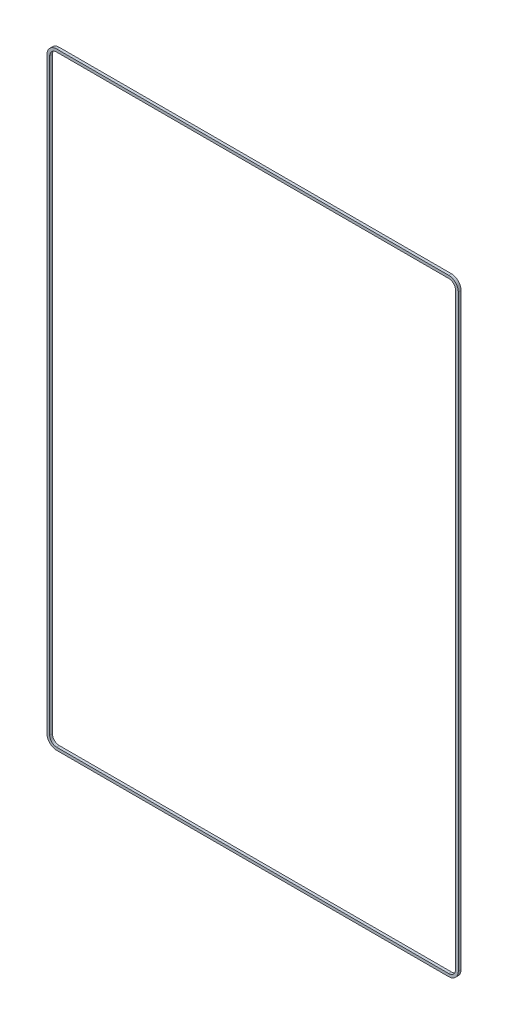
SolidWorks part; units mm, degrees
ref_plane "Front Plane" through (0, 0, 0) normal (0, 0, 1) x (1, 0, 0)
ref_plane "Top Plane" through (0, 0, 0) normal (0, 1, 0) x (1, 0, 0)
ref_plane "Right Plane" through (0, 0, 0) normal (1, 0, 0) x (0, 0, -1)
sketch "Sketch1" plane through (0, 0, 0) normal (0, 0, 1) x (1, 0, 0)
  line L0 (4.318, -2.032) -> (258.318, -2.032) construction
  line L1 (4.318, 0) -> (258.318, 0) construction
  line L2 (0, 4.318) -> (0, 385.318) construction
  line L3 (4.318, 389.636) -> (258.318, 389.636) construction
  line L4 (262.636, 4.318) -> (262.636, 385.318) construction
  line L5 (264.668, 4.318) -> (264.668, 385.318) construction
  line L6 (4.318, 391.668) -> (258.318, 391.668) construction
  line L7 (-2.032, 4.318) -> (-2.032, 385.318) construction
  line L8 (-0.127, 4.318) -> (-0.127, 385.318)
  line L9 (4.318, 389.763) -> (258.318, 389.763)
  line L10 (262.763, 4.318) -> (262.763, 385.318)
  line L11 (4.318, -0.127) -> (258.318, -0.127)
  line L12 (-1.905, 4.318) -> (-1.905, 385.318)
  line L13 (4.318, 391.541) -> (258.318, 391.541)
  line L14 (264.541, 4.318) -> (264.541, 385.318)
  line L15 (4.318, -1.905) -> (258.318, -1.905)
  arc A0 (4.318, 0) -> (0, 4.318) centre (4.318, 4.318) cw construction
  arc A1 (258.318, 0) -> (262.636, 4.318) centre (258.318, 4.318) ccw construction
  arc A2 (258.318, 389.636) -> (262.636, 385.318) centre (258.318, 385.318) cw construction
  arc A3 (0, 385.318) -> (4.318, 389.636) centre (4.318, 385.318) cw construction
  arc A4 (258.318, -2.032) -> (264.668, 4.318) centre (258.318, 4.318) ccw construction
  arc A5 (258.318, 391.668) -> (264.668, 385.318) centre (258.318, 385.318) cw construction
  arc A6 (-2.032, 385.318) -> (4.318, 391.668) centre (4.318, 385.318) cw construction
  arc A7 (4.318, -2.032) -> (-2.032, 4.318) centre (4.318, 4.318) cw construction
  arc A8 (-0.127, 385.318) -> (4.318, 389.763) centre (4.318, 385.318) cw
  arc A9 (258.318, 389.763) -> (262.763, 385.318) centre (258.318, 385.318) cw
  arc A10 (258.318, -0.127) -> (262.763, 4.318) centre (258.318, 4.318) ccw
  arc A11 (4.318, -0.127) -> (-0.127, 4.318) centre (4.318, 4.318) cw
  arc A12 (-1.905, 385.318) -> (4.318, 391.541) centre (4.318, 385.318) cw
  arc A13 (258.318, 391.541) -> (264.541, 385.318) centre (258.318, 385.318) cw
  arc A14 (258.318, -1.905) -> (264.541, 4.318) centre (258.318, 4.318) ccw
  arc A15 (4.318, -1.905) -> (-1.905, 4.318) centre (4.318, 4.318) cw
  point P7 (0, 0)
  point P10 (262.636, 0)
  point P13 (262.636, 389.636)
  point P16 (0, 389.636)
  dimension "D3" = 4.318
  dimension "D1" = 389.636
  dimension "D2" = 262.636
  dimension "D4" = 2.032
  dimension "D5" = 0.127
  dimension "D6" = 1.778
extrude "Boss-Extrude1" add sketch "Sketch1" along normal blind 1.778 contours A15 L15 A14 L14 A13 L13 A12 L12 L11 A11 L8 A8 L9 A9 L10 A10 region at (-1.4298, 194.818, 0)
